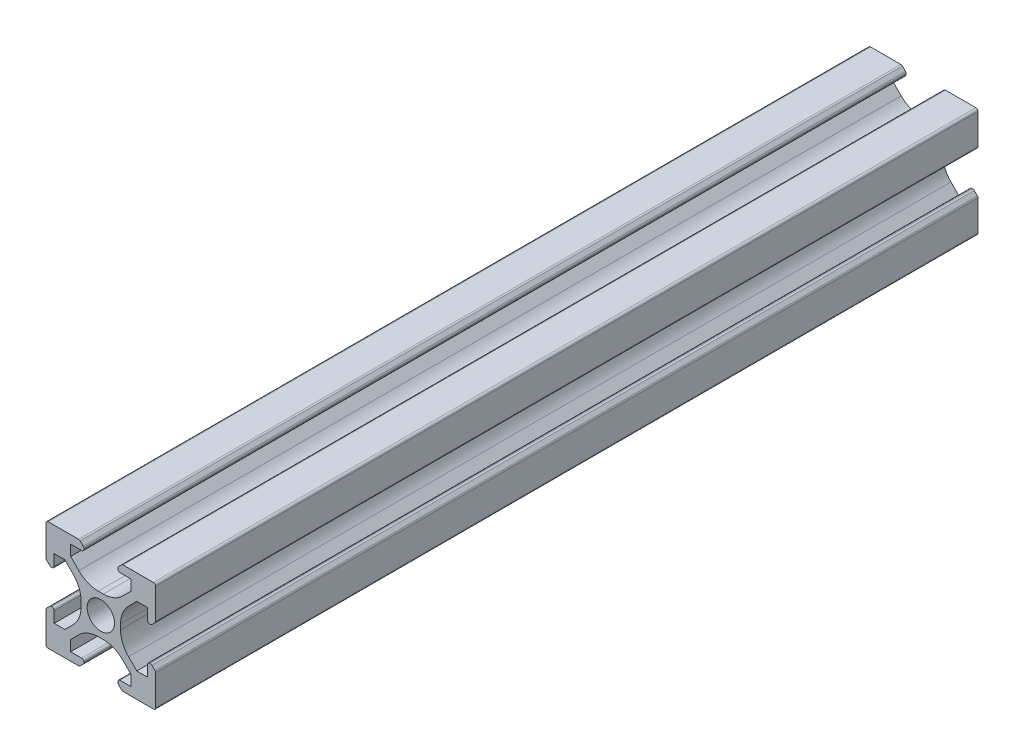
SolidWorks part; units mm, degrees
material "6063-T83"
ref_plane "Plano frontal" through (0, 0, 0) normal (0, 0, 1) x (1, 0, 0)
ref_plane "Plano superior" through (0, 0, 0) normal (0, 1, 0) x (1, 0, 0)
ref_plane "Plano direito" through (0, 0, 0) normal (1, 0, 0) x (0, 0, -1)
sketch "Esboço1" plane through (0, 0, 0) normal (0, 0, 1) x (1, 0, 0)
  line L0 (-9.0343, 3.1) -> (-8.9, 3.1)
  line L3 (-10, 10) -> (-4.0657, 10)
  line L5 (-10, -10) -> (10, 10) construction
  line L6 (-10, 10) -> (10, -10) construction
  line L7 (-8.5, 3.5) -> (-8.5, 5.5)
  line L8 (-10, 0) -> (10, 0) construction
  line L9 (0, 10) -> (0, -10) construction
  line L12 (-8.5, 5.5) -> (-6.5607, 5.5)
  line L15 (-6.5607, 5.5) -> (-5.0645, 4.0038)
  line L16 (-3.6, 0.4683) -> (-3.6, 0)
  line L17 (-0.4683, 3.6) -> (0, 3.6)
  line L18 (-5.5, 6.5607) -> (-4.0038, 5.0645)
  line L21 (-5.5, 8.5) -> (-5.5, 6.5607)
  line L24 (-3.5, 8.5) -> (-5.5, 8.5)
  line L25 (-3.1, 9.0343) -> (-3.1, 8.9)
  line L44 (-10, 4.0657) -> (-10, 10)
  line L45 (-9.8828, 3.7828) -> (-9.3172, 3.2172)
  line L46 (-3.7828, 9.8828) -> (-3.2172, 9.3172)
  line L47 (-3.6, 0) -> (-2.5, 0)
  line L48 (0, 3.6) -> (0, 2.5)
  arc A0 (-3.5, 8.5) -> (-3.1, 8.9) centre (-3.5, 8.9) ccw
  arc A1 (-3.7828, 9.8828) -> (-4.0657, 10) centre (-4.0657, 9.6) ccw
  arc A2 (-10, 4.0657) -> (-9.8828, 3.7828) centre (-9.6, 4.0657) ccw
  arc A3 (-8.5, 3.5) -> (-8.9, 3.1) centre (-8.9, 3.5) cw
  arc A4 (-3.2172, 9.3172) -> (-3.1, 9.0343) centre (-3.5, 9.0343) cw
  arc A5 (-9.3172, 3.2172) -> (-9.0343, 3.1) centre (-9.0343, 3.5) ccw
  arc A6 (-3.6, 0.4683) -> (-5.0645, 4.0038) centre (-8.6, 0.4683) ccw
  arc A7 (-4.0038, 5.0645) -> (-0.4683, 3.6) centre (-0.4683, 8.6) ccw
  circle A8 centre (0, 0) radius 2.5
  point P6 (-10, 3.1)
  point P28 (-3.1, 8.5)
  point P31 (-3.1, 10)
  point P33 (-3.9, 10)
  point P36 (-10, 3.9)
  point P39 (-8.5, 3.1)
  point P42 (-3.1, 9.2)
  point P45 (-9.2, 3.1)
  point P48 (-3.6, 2.5393)
  point P51 (-2.5393, 3.6)
  dimension "D5" = 10
  dimension "D9" = 0.4
  dimension "D10" = 0.4
  dimension "D11" = 5
  dimension "D12" = 5
  dimension "D13" = 5
  dimension "D1" = 6.9
  dimension "D2" = 1.5
  dimension "D3" = 3.6
  dimension "D4" = 1.5
  dimension "D6" = 2.4
  dimension "D7" = 3.6
  dimension "D8" = 45
extrude "Ressalto-extrusão1" add sketch "Esboço1" along normal blind 150 contours A4 A3 L3 A0 L17 L18 L21 L24 L25 L0 L7 L12 L15 L16 region at (-5.9987, 5.9987, 0)
sketch "Esboço3" plane through (0, 0, 0) normal (1, 0, 0) x (0, 0, -1)
  line L0 (0, 0) -> (-150, 0) construction
  line L1 (-150, 2.5) -> (-150, 0) construction
pattern_circular "PadrãoCircular1" count 4 every 90 about axis through (0, 0, 0) along (0, 0, 1) of "Ressalto-extrusão1"
fillet "Filete1" radius 0.4 4 edges at (-10, -10, 75) (-10, 10, 75) (10, -10, 75) (10, 10, 75)
